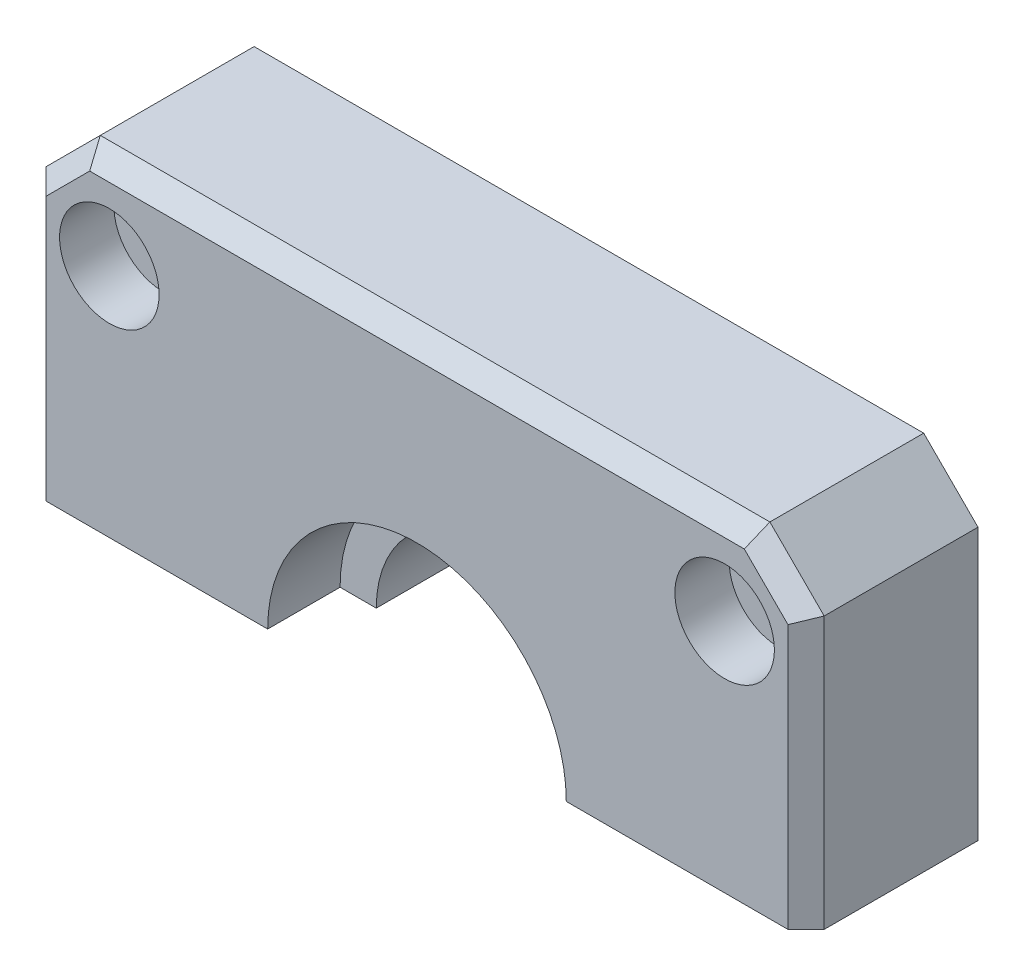
SolidWorks part; units mm, degrees
ref_plane "前基準面" through (0, 0, 0) normal (0, 0, 1) x (1, 0, 0)
ref_plane "上基準面" through (0, 0, 0) normal (0, 1, 0) x (1, 0, 0)
ref_plane "右基準面" through (0, 0, 0) normal (1, 0, 0) x (0, 0, -1)
sketch "草圖1" plane through (0, 0, 0) normal (0, 0, 1) x (1, 0, 0)
  line L0 (0, 0) -> (0, 40) construction
  line L1 (-20.5, 40) -> (20.5, 40)
  line L2 (20.5, 40) -> (20.5, 30)
  line L3 (-20.5, 40) -> (-20.5, 30)
  line L4 (44.891, -2.2465) -> (36.2308, 2.7535)
  line L5 (44.891, -2.2465) -> (24.391, -37.7535)
  line L6 (24.391, -37.7535) -> (15.7308, -32.7535)
  line L7 (-24.391, -37.7535) -> (-15.7308, -32.7535)
  line L8 (-24.391, -37.7535) -> (-44.891, -2.2465)
  line L9 (-44.891, -2.2465) -> (-36.2308, 2.7535)
  line L10 (-36.2308, 2.7535) -> (-20.5, 30)
  line L11 (20.5, 30) -> (36.2308, 2.7535)
  line L12 (15.7308, -32.7535) -> (-15.7308, -32.7535)
  line L13 (0, 0) -> (34.641, -20) construction
  line L14 (0, 0) -> (-34.641, -20) construction
  circle A0 centre (0, 0) radius 18
  point P6 (0, 0)
  point P9 (0, 40)
  point P22 (0, 0)
  point P23 (0, 0)
  dimension "D1" = 36
  dimension "D2" = 40
  dimension "D3" = 20.5
  dimension "D4" = 10
  dimension "D6" = 20.5
  dimension "D7" = 3
  dimension "D8" = 40
  dimension "D9" = 40
  dimension "D10" = 72.7535
  dimension "D5" = 3
extrude "填料-伸長1" add sketch "草圖1" along normal blind 20
sketch "草圖2" plane through (-20.5, 0, 0) normal (-1, 0, 0) x (0, 0, 1)
  line L0 (20, 35) -> (0, 35) construction
  line L1 (20, 40) -> (20, 30) construction
  line L2 (0, 40) -> (0, 30) construction
  circle A0 centre (15, 35) radius 2.75
  dimension "D1" = 5.5
  dimension "D2" = 5
extrude "除料-伸長1" cut sketch "草圖2" against normal through all
pattern_circular "環狀複製排列1" count 3 over 360 about axis through (0, 0, 20) along (0, 0, 1) of "除料-伸長1"
sketch "草圖3" plane through (-20.5, 0, 0) normal (-1, 0, 0) x (0, 0, 1)
  line L0 (0, 40) -> (2.6795, 30) construction
  line L3 (20, 30) -> (0, 30) construction
  line L4 (0, 40) -> (0, 30) construction
  dimension "D1" = 15
sketch "草圖4" plane through (0, 0, 0) normal (0, 0, -1) x (-1, 0, 0)
  point P0 (-20.5, 40)
ref_plane "平面1" through (0, 2.6795, 10) normal (0, 0.2588, 0.9659) x (1, 0, 0)
sketch "草圖5" plane through (0, 2.6795, 10) normal (0, 0.2588, 0.9659) x (1, 0, 0)
  line L0 (0, 38.637) -> (0, 0) construction
  line L1 (20.5, 38.637) -> (-20.5, 38.637) construction
  line L2 (-14.5, 33.637) -> (14.5, 33.637) construction
  line L3 (-14.5, 33.637) -> (-14.5, 38.637)
  line L4 (-15, 38.637) -> (15, 38.637)
  line L5 (-15, 38.637) -> (-15, 18.637)
  line L6 (-15, 18.637) -> (15, 18.637)
  line L7 (15, 38.637) -> (15, 18.637)
  line L8 (14.5, 33.637) -> (14.5, 38.637)
  arc A0 (-9.4338, 22.6255) -> (9.4338, 22.6255) centre (0, 33.637) ccw
  arc A1 (-11.0115, 24.2032) -> (-9.4338, 22.6255) centre (-12, 21.637) ccw
  arc A2 (11.0115, 24.2032) -> (9.4338, 22.6255) centre (12, 21.637) cw
  arc A3 (11.0115, 24.2032) -> (14.5, 33.637) centre (0, 33.637) ccw
  arc A4 (-14.5, 33.637) -> (-11.0115, 24.2032) centre (0, 33.637) ccw
  arc A5 (13.6107, 38.637) -> (-13.6107, 38.637) centre (0, 33.637) ccw
  point P17 (0, 18.637)
  dimension "D1" = 29
  dimension "D3" = 5.5
  dimension "D2" = 5
  dimension "D4" = 12
  dimension "D5" = 12
  dimension "D6" = 30
  dimension "D7" = 20
  dimension "D8" = 0.5
  dimension "D9" = 0.5
  dimension "D10" = 0.8893
  dimension "D11" = 0.8893
  dimension "D12" = 14.5
  dimension "D13" = 14.5
extrude "除料-伸長2" cut sketch "草圖5" along normal blind 9 and the other way through all contours A2 A3 L4 A1 A0
sketch "草圖6" plane through (0, 2.6795, 10) normal (0, 0.2588, 0.9659) x (1, 0, 0)
  line L0 (0, 0) -> (0, 38.637) construction
  line L2 (-15, 38.637) -> (15, 38.637)
  line L3 (-15, 38.637) -> (-15, 18.637)
  line L4 (-15, 18.637) -> (15, 18.637)
  line L5 (15, 38.637) -> (15, 18.637)
extrude "除料-伸長3" cut sketch "草圖6" against normal through all and the other way blind 5
sketch "草圖7" plane through (0, 3.9736, 14.8296) normal (0, -0.2588, -0.9659) x (-1, 0, 0)
  circle A0 centre (12, 21.637) radius 2.75
  circle A1 centre (-12, 21.637) radius 2.75
extrude "除料-伸長4" cut sketch "草圖7" against normal blind 5
pattern_circular "環狀複製排列2" count 3 over 360 about axis through (0, 0, 0) along (0, 0, 1) of "除料-伸長2", "除料-伸長3", "除料-伸長4"
fillet "圓角1" radius 3 6 edges at (-43.516, -4.628, 0) (-25.766, -35.372, 0) (25.766, -35.372, 0) (43.516, -4.628, 0) (17.75, 40, 0) (-17.75, 40, 0)
sketch "草圖11" plane through (0, 0, 20) normal (0, 0, 1) x (1, 0, 0)
  line L0 (0, 40) -> (0, -32.7535) construction
  line L1 (20.5, 40) -> (-20.5, 40) construction
  line L2 (-15.7308, -32.7535) -> (15.7308, -32.7535) construction
  line L3 (-14.5, 18) -> (-21.5, 18)
  line L4 (-14.5, -18) -> (-21.5, -18)
  line L5 (-21.5, 18) -> (-21.5, -18)
  line L6 (14.5, 18) -> (14.5, 10.563)
  line L7 (-14.5, 18) -> (-14.5, 10.563)
  line L8 (0, 0) -> (-21.5, 0) construction
  line L9 (21.5, 18) -> (21.5, -18)
  line L10 (14.5, -18) -> (21.5, -18)
  line L11 (14.5, 18) -> (21.5, 18)
  line L12 (-14.5, -10.563) -> (-14.5, -18)
  line L13 (14.5, -10.563) -> (14.5, -18)
  circle A0 centre (0, 0) radius 14.5 construction
  circle A1 centre (0, 0) radius 17.9395
  circle M20 centre (0, 0) radius 18
  dimension "D1" = 29
  dimension "D2" = 7
  dimension "D3" = 14.5
  dimension "D4" = 18
extrude "填料-伸長2" add sketch "草圖11" along normal blind 20 contours L12 L7 L3 L5 L4 M20 | L13 L10 L9 L11 L6 M20
sketch "草圖12" plane through (0, 0, 40) normal (0, 0, 1) x (1, 0, 0)
  line L0 (-14.5, 18) -> (-21.5, 18) construction
  line L1 (21.5, -18) -> (-21.5, -18)
  line L2 (21.5, -18) -> (21.5, 18)
  line L3 (21.5, 18) -> (-21.5, 18)
  line L4 (-21.5, -18) -> (-21.5, 18)
  circle A0 centre (0, 0) radius 8
  dimension "D1" = 16
extrude "填料-伸長3" add sketch "草圖12" along normal blind 9
chamfer "導角1" distance 1.5 angle 60 1 edges at (0, 18, 40) first distance on face at (0, 18, 32.25)
sketch "草圖13" plane through (0, 18, 0) normal (0, 1, 0) x (1, 0, 0)
  line L0 (0, -49) -> (0, 0) construction
  line L1 (15, -46) -> (-15, -46)
  line L2 (15, -46) -> (15, -16)
  line L3 (15, -16) -> (-15, -16)
  line L4 (-15, -46) -> (-15, -16)
  line L5 (21.5, -49) -> (-21.5, -49) construction
  line L6 (15, -31) -> (-15, -31) construction
  circle A0 centre (0, -31) radius 14.5
  circle A1 centre (12, -43) radius 1.5
  circle A2 centre (-12, -43) radius 1.5
  point P9 (0, -46)
  dimension "D3" = 29
  dimension "D7" = 3
  dimension "D1" = 30
  dimension "D2" = 30
  dimension "D4" = 12
  dimension "D5" = 12
  dimension "D6" = 18
extrude "除料-伸長7" cut sketch "草圖13" against normal blind 20 contours A2 | A1
sketch "草圖15" plane through (0, 18, 0) normal (0, 1, 0) x (1, 0, 0)
  line L0 (15, -16) -> (-15, -16) construction
  line L1 (14.5, -40) -> (-14.5, -40)
  line L2 (14.5, -40) -> (14.5, -16)
  line L3 (14.5, -16) -> (-14.5, -16)
  line L4 (-14.5, -40) -> (-14.5, -16)
  line L5 (-14.5, -41.5) -> (-14.5, -20) construction
  line L6 (14.5, -41.5) -> (14.5, -20) construction
  line L7 (-14.5, -40) -> (14.5, -40) construction
extrude "除料-伸長9" cut sketch "草圖15" against normal blind 80
fillet "圓角2" radius 2.5 3 edges at (-34.641, -20, 20) (34.641, -20, 20) (0, 40, 20)
fillet "圓角3" radius 1 30 edges at (-20.5, 33.75, 20) (-20.5, 39.2678, 19.2678) (-20.5, 33.5, 0) (-20.5, 39.1213, 0.8787) (-39.4784, 0.8785, 20) (-44.2569, -1.8804, 19.2678) (-39.2619, 1.0035, 0) (-44.1301, -1.8071, 0.8787) (-18.9784, -34.6285, 20) (-23.7569, -37.3874, 19.2678) (-18.7619, -34.5035, 0) (-23.6301, -37.3142, 0.8787) (18.9784, -34.6285, 20) (23.7569, -37.3874, 19.2678) (18.7619, -34.5035, 0) (23.6301, -37.3142, 0.8787) (39.4784, 0.8785, 20) (44.2569, -1.8804, 19.2678) (39.2619, 1.0035, 0) (44.1301, -1.8071, 0.8787) (20.5, 33.75, 20) (20.5, 39.2678, 19.2678) (20.5, 33.5, 0) (20.5, 39.1213, 0.8787) (-20.5, 40, 10.25) (-44.891, -2.2465, 10.25) (-24.391, -37.7535, 10.25) (24.391, -37.7535, 10.25) (44.891, -2.2465, 10.25) (20.5, 40, 10.25)
sketch "草圖17" plane through (0, 18, 0) normal (0, 1, 0) x (1, 0, 0)
  line L0 (0, 0) -> (0, -49) construction
  line L1 (15, -31) -> (-15, -31) construction
  line L2 (14.5, -21.5528) -> (11, -21.5528)
  line L3 (14.5, -41.5) -> (14.5, -20) construction
  line L4 (8.8318, -16) -> (8.8318, -19.5)
  line L5 (15, -16) -> (-15, -16) construction
  line L6 (14.5, -21.5528) -> (14.5, -16)
  line L7 (14.5, -16) -> (8.8318, -16)
  line L8 (-14.5, -16) -> (-8.8318, -16)
  line L9 (-14.5, -21.5528) -> (-14.5, -16)
  line L10 (-8.8318, -16) -> (-8.8318, -19.5)
  line L11 (-14.5, -21.5528) -> (-11, -21.5528)
  circle A0 centre (12, -19) radius 1.5
  arc A1 (11, -21.5528) -> (8.8318, -19.5) centre (0, -31) ccw
  arc A2 (-11, -21.5528) -> (-8.8318, -19.5) centre (0, -31) cw
  circle A3 centre (-12, -19) radius 1.5
  dimension "D3" = 3
  dimension "D4" = 29
  dimension "D1" = 12
  dimension "D2" = 12
  dimension "D5" = 3.5
  dimension "D6" = 3.5
extrude "填料-伸長4" add sketch "草圖17" against normal blind 5
sketch "草圖18" plane through (0, 0, 16) normal (0, 0, -1) x (-1, 0, 0)
  circle A0 centre (0, 0) radius 18
extrude "除料-伸長11" cut sketch "草圖18" against normal up to surface (5.5528 mm away) up to face at (-12.75, 15.5, 21.5528)
sketch "草圖14" plane through (0, 18, 0) normal (0, 1, 0) x (1, 0, 0)
  line L1 (-15, -46) -> (-15, -16) construction
  line L2 (15, -16) -> (-15, -16)
  line L3 (15, -16) -> (15, -21.5528)
  line L4 (15, -21.5528) -> (-15, -21.5528)
  line L7 (-15, -16) -> (-15, -21.5528)
  line L8 (11, -21.5528) -> (14.5, -21.5528) construction
extrude "除料-伸長14" cut sketch "草圖14" along normal blind 13
chamfer "導角3" distance 3 angle 46 1 edges at (0, 31, 20) first distance on face at (0, -0.1461, 20)
ref_plane "平面2" through (0, -15.1166, 26.1827) normal (0, -0.5, 0.866) x (-1, 0, 0)
sketch "草圖19" plane through (0, -15.1166, 26.1827) normal (0, -0.5, 0.866) x (-1, 0, 0)
  line L0 (0, 0) -> (0, 28.3654) construction
  line L1 (17.7308, 28.3654) -> (-17.7308, 28.3654) construction
  circle A0 centre (0, 19.7998) radius 2.5
  dimension "D1" = 5
extrude "除料-伸長15" cut sketch "草圖19" against normal through all both and the other way through all
sketch "草圖20" plane through (0, -15.1166, 26.1827) normal (0, -0.5, 0.866) x (-1, 0, 0)
  circle A0 centre (0, 19.7998) radius 2.75
  dimension "D1" = 5.5
extrude "除料-伸長16" cut sketch "草圖20" against normal blind 12
fillet "圓角4" radius 3 2 edges at (8.5956, -32.7535, 16) (-8.5956, -32.7535, 16)
fillet "圓角5" radius 1 5 edges at (0, -32.7535, 0) (28.3654, 16.3768, 20) (28.3654, 16.3768, 0) (-28.3654, 16.3768, 20) (-28.3654, 16.3768, 0)
chamfer "導角4" distance 3 angle 45 4 edges at (21.5, -18, 34.5) (-21.5, -18, 34.5) (-21.5, 18, 34.5) (21.5, 18, 34.5)
fillet "圓角6" radius 1 6 edges at (14.5, -31.8748, 15.1213) (-14.5, -31.8748, 15.1213) (14.5, -25.3768, 20) (14.5, -20.2094, 16) (-14.5, -20.2094, 16) (-14.5, -25.3768, 20)
chamfer "導角5" distance 2.5 angle 45 12 edges at (14.7929, -18, 19.7071) (16.75, 18, 20) (20, 16.5, 20) (21.5, 0, 20) (20, -16.5, 20) (17, -18, 20) (-14.7929, -18, 19.7071) (-16.75, 18, 20) (-20, 16.5, 20) (-17, -18, 20) (-20, -16.5, 20) (-21.5, 0, 20)
sketch "草圖21" plane through (-20.5, 0, 0) normal (-1, 0, 0) x (0, 0, 1)
  circle A0 centre (15, 35) radius 2.75
extrude "填料-伸長5" add sketch "草圖21" against normal blind 31 from offset 5 offset against normal yes
pattern_circular "環狀複製排列3" count 3 over 360 about axis through (0, 0, 0) along (0, 0, 1) of "填料-伸長5"
sketch "草圖22" plane through (0, 0, 49) normal (0, 0, 1) x (1, 0, 0)
  line L0 (-21.5, 15) -> (-18.5, 18)
  line L1 (-18.5, 18) -> (18.5, 18)
  line L2 (18.5, 18) -> (21.5, 15)
  line L3 (21.5, 15) -> (21.5, 0)
  line L4 (21.5, -15) -> (21.5, 15) construction
  line L5 (21.5, 0) -> (6.25, 0)
  line L6 (-21.5, 15) -> (-21.5, -15) construction
  line L7 (-21.5, 0) -> (-21.5, 15)
  line L8 (-6.25, 0) -> (-21.5, 0)
  arc A0 (6.25, 0) -> (-6.25, 0) centre (0, 0) ccw
  dimension "D1" = 12.5
extrude "填料-伸長6" add sketch "草圖22" along normal blind 9.5
sketch "草圖16" plane through (0, 0, 49) normal (0, 0, 1) x (1, 0, 0)
  line L0 (0, -18) -> (0, 18) construction
  line L1 (-18.5, -18) -> (18.5, -18) construction
  line L2 (21.5, 18) -> (-21.5, 18) construction
  line L3 (21.5, 0) -> (-21.5, 0) construction
  line L5 (-21.5, 18) -> (-21.5, -18) construction
  circle A0 centre (17, -13) radius 1.5
  circle A1 centre (-17, -13) radius 1.5
  circle A2 centre (-17, 13) radius 1.5
  circle A3 centre (17, 13) radius 1.5
  dimension "D1" = 3
  dimension "D2" = 17
  dimension "D3" = 13
extrude "除料-伸長10" cut sketch "草圖16" along normal through all
sketch "草圖23" plane through (0, -18, 0) normal (0, -1, 0) x (1, 0, 0)
  line L1 (-49.4886, 49) -> (52.9623, 49)
  line L2 (-49.4886, 49) -> (-49.4886, -10.055)
  line L3 (-49.4886, -10.055) -> (52.9623, -10.055)
  line L4 (52.9623, 49) -> (52.9623, -10.055)
extrude "除料-伸長17" cut sketch "草圖23" against normal through all both and the other way through all
sketch "草圖24" plane through (0, 0, 0) normal (0, -1, 0) x (1, 0, 0)
  line L0 (0, 58.5) -> (0, 49) construction
  line L1 (6.25, 58.5) -> (-6.25, 58.5) construction
  line L2 (-6.25, 49) -> (6.25, 49) construction
  line L3 (-21.5, 53.75) -> (0, 53.75) construction
  line L4 (-21.5, 58.5) -> (-21.5, 49) construction
  circle A0 centre (-11.5, 53.75) radius 2.75
  circle A1 centre (11.5, 53.75) radius 2.75
  dimension "D1" = 5.5
  dimension "D2" = 10
sketch "草圖25" plane through (0, 0, 58.5) normal (0, 0, 1) x (1, 0, 0)
  circle A0 centre (0, 0) radius 8.25
  dimension "D1" = 16.5
extrude "除料-伸長18" cut sketch "草圖25" against normal blind 4
extrude "除料-伸長19" cut sketch "草圖24" against normal blind 6
sketch "草圖26" plane through (0, 0, 58.5) normal (0, 0, 1) x (1, 0, 0)
  circle A0 centre (-17, 13) radius 2.75
  circle A1 centre (17, 13) radius 2.75
  dimension "D1" = 5.5
  dimension "D2" = 5.5
extrude "除料-伸長20" cut sketch "草圖26" against normal blind 3
chamfer "導角6" distance 1 angle 45 5 edges at (21.5, 7.5, 58.5) (20, 16.5, 58.5) (-21.5, 7.5, 58.5) (-20, 16.5, 58.5) (0, 18, 58.5)
